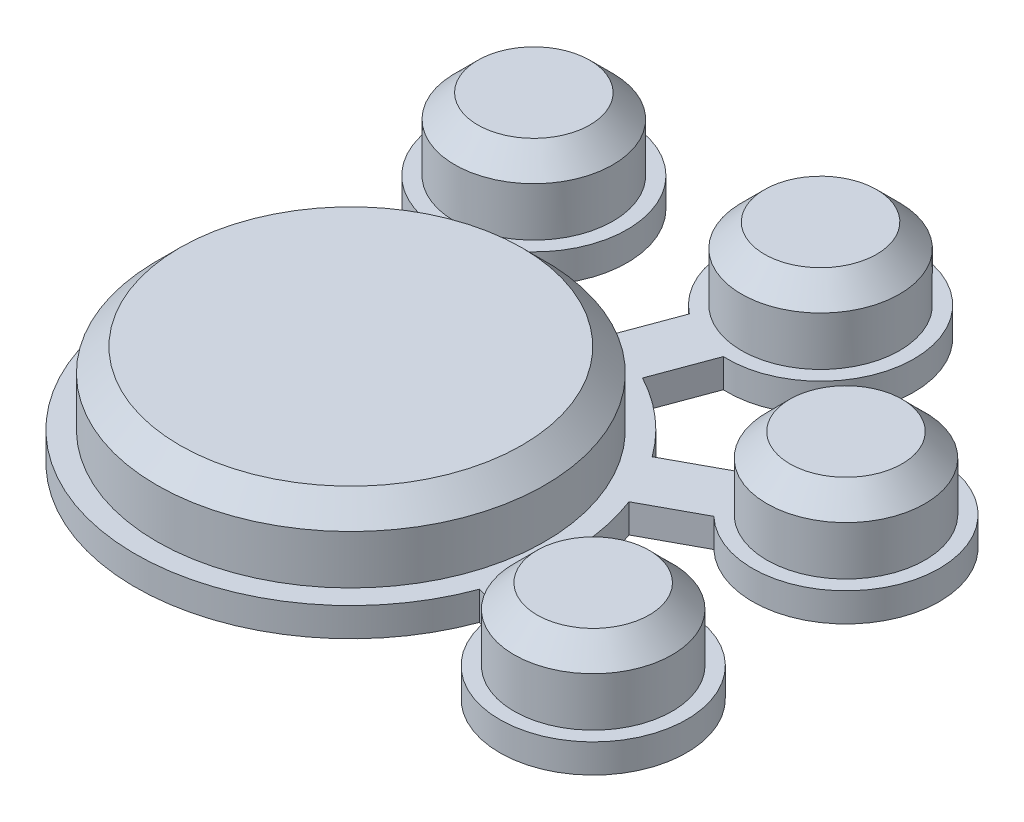
SolidWorks part; units mm, degrees
ref_plane "前视基准面" through (0, 0, 0) normal (0, 0, 1) x (1, 0, 0)
ref_plane "上视基准面" through (0, 0, 0) normal (0, 1, 0) x (1, 0, 0)
ref_plane "右视基准面" through (0, 0, 0) normal (1, 0, 0) x (0, 0, -1)
other "Configuration Table"
sketch "草图1" plane through (0, 0, 0) normal (0, 1, 0) x (1, 0, 0)
  line L0 (1.2, 1.4) -> (1.2, -9.6) construction
  line L1 (1.2, 1.4) -> (11.3256, -2.898) construction
  line L2 (1.2, 1.4) -> (11.1694, 6.0488) construction
  line L3 (1.2, 1.4) -> (4.4161, 11.9194) construction
  line L4 (1.2, 1.4) -> (-4.4654, 10.8288) construction
  line L5 (0, 0) -> (11.3256, -2.898) construction
  line L6 (0, 0) -> (11.1694, 6.0488) construction
  line L7 (0, 0) -> (4.4161, 11.9194) construction
  line L8 (0, 0) -> (-4.4654, 10.8288) construction
  line L9 (8.0761, -2.8407) -> (7.0436, -2.5765)
  line L10 (7.4154, -1.1233) -> (8.4479, -1.3875)
  line L11 (8.9264, 3.6969) -> (7.0123, 2.6603)
  line L12 (7.974, 5.4556) -> (6.0599, 4.419)
  line L13 (4.2795, 8.6722) -> (3.5201, 6.6226)
  line L14 (2.404, 9.3671) -> (1.6447, 7.3174)
  line L15 (-2.5665, 8.1913) -> (-2.1515, 7.1848)
  line L16 (-3.9532, 7.6195) -> (-3.5382, 6.613)
  circle A0 centre (0, 0) radius 7.5
  circle A1 centre (1.2, 1.4) radius 11 construction
  circle A2 centre (-4.4654, 10.8288) radius 3.25
  circle A3 centre (4.4161, 11.9194) radius 3.25
  circle A4 centre (11.1694, 6.0488) radius 3.25
  circle A5 centre (11.3256, -2.898) radius 3.25
  dimension "D1" = 15
  dimension "D2" = 22
  dimension "D9" = 6.5
  dimension "D3" = 1.2
  dimension "D4" = 1.4
  dimension "D5" = 67
  dimension "D6" = 48
  dimension "D7" = 48
  dimension "D8" = 48
  dimension "D10" = 1.5
  dimension "D11" = 2
  dimension "D12" = 2
  dimension "D13" = 1.5
  dimension "D14" = 0.75
  dimension "D15" = 1
  dimension "D16" = 1
  dimension "D17" = 0.75
extrude "凸台-拉伸1" add sketch "草图1" along normal blind 1 contours A2 | A2 L16 A0 L15 | A0 | A3 | A3 L14 A0 L13 | A4 L12 A0 L11 | A4 | A5 | A5 L10 A0 L9 region at (7.7297, 0, 1.9779) region at (11.3256, 0, 2.898) region at (0, 0, 0) region at (-3.0461, 0, -7.3869) region at (-4.4654, 0, -10.8288) region at (2.9516, 0, -7.9667) region at (7.4667, 0, -4.0436) region at (4.4161, 0, -11.9194) region at (11.1694, 0, -6.0488)
sketch "草图2" plane through (0, 1, 0) normal (0, 1, 0) x (1, 0, 0)
  circle A0 centre (0, 0) radius 6.75
  circle A1 centre (-4.4654, 10.8288) radius 2.75
  circle A2 centre (4.4161, 11.9194) radius 2.75
  circle A3 centre (11.1694, 6.0488) radius 2.75
  circle A4 centre (11.3256, -2.898) radius 2.75
  dimension "D1" = 13.5
  dimension "D2" = 5.5
extrude "凸台-拉伸2" add sketch "草图2" along normal blind 2.5
chamfer "倒角1" distance 0.8 angle 45 5 edges at (0, 3.5, 6.75) (11.3256, 3.5, 5.648) (11.1694, 3.5, -3.2988) (4.4161, 3.5, -9.1694) (-4.4654, 3.5, -8.0788)
sketch "草图3" plane through (0, 0, 0) normal (0, -1, 0) x (1, 0, 0)
  circle A0 centre (0, 0) radius 1
  circle A1 centre (11.3256, 2.898) radius 1
  circle A2 centre (11.1694, -6.0488) radius 1
  circle A3 centre (4.4161, -11.9194) radius 1
  circle A4 centre (-4.4654, -10.8288) radius 1
  dimension "D1" = 2
extrude "凸台-拉伸3" add sketch "草图3" along normal blind 0.55
